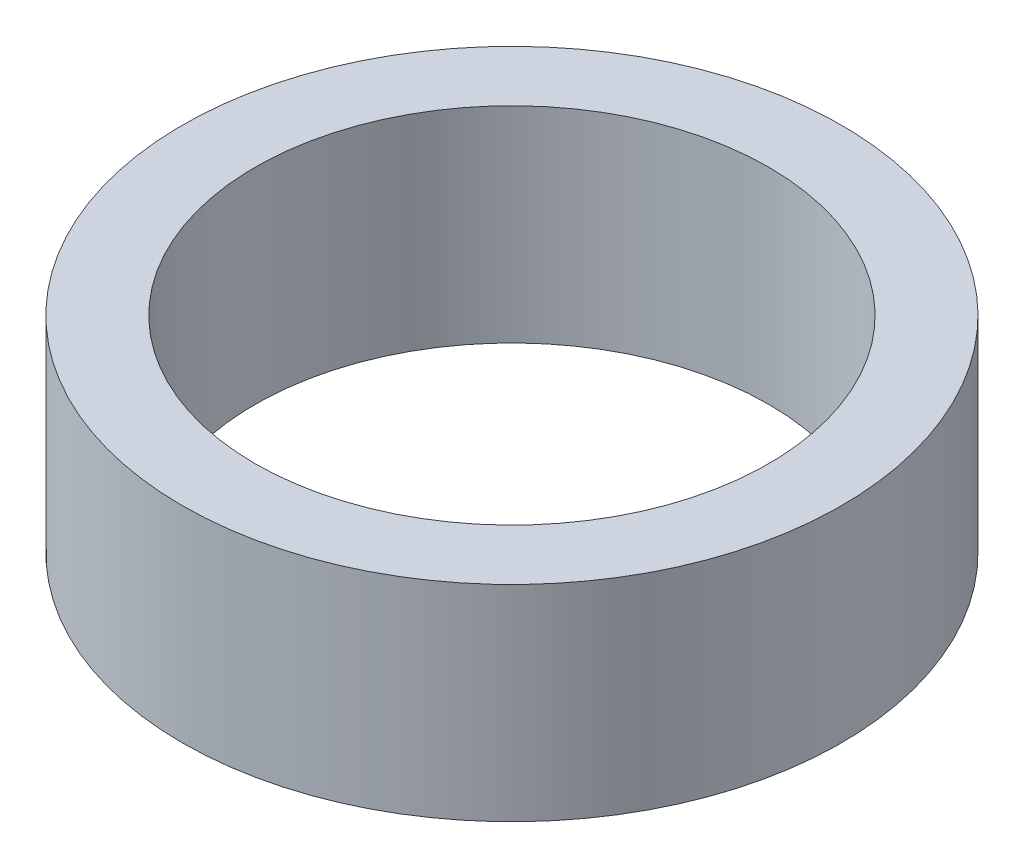
SolidWorks part; units mm, degrees
ref_plane "Plan de face" through (0, 0, 0) normal (0, 0, 1) x (1, 0, 0)
ref_plane "Plan de dessus" through (0, 0, 0) normal (0, 1, 0) x (1, 0, 0)
ref_plane "Plan de droite" through (0, 0, 0) normal (1, 0, 0) x (0, 0, -1)
sketch "Esquisse1" plane through (0, 0, 0) normal (0, 1, 0) x (1, 0, 0)
  circle A0 centre (0, 0) radius 3.85
  circle A1 centre (0, 0) radius 3
  point P5 (0, -0.0273)
  dimension "D1" = 7.7
  dimension "D2" = 6
extrude "Boss.-Extru.1" add sketch "Esquisse1" along normal blind 2.4 contours A0 | A1
